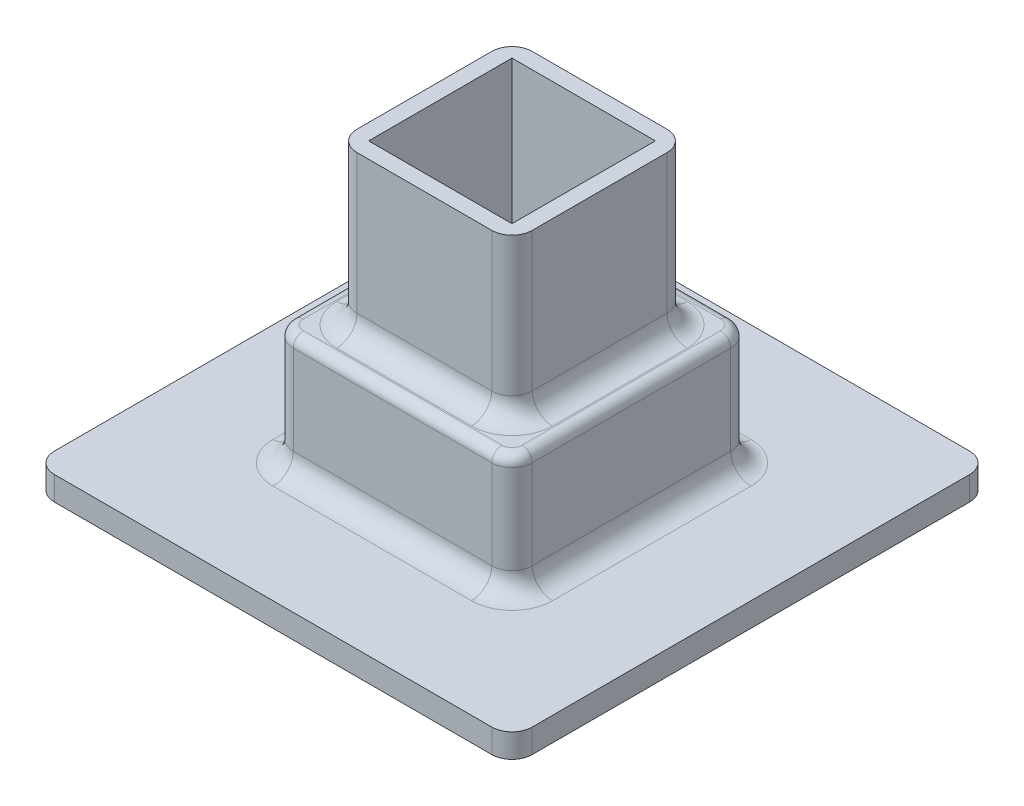
SolidWorks part; units mm, degrees
material "ABS"
ref_plane "Front Plane" through (0, 0, 0) normal (0, 0, 1) x (1, 0, 0)
ref_plane "Top Plane" through (0, 0, 0) normal (0, 1, 0) x (1, 0, 0)
ref_plane "Right Plane" through (0, 0, 0) normal (1, 0, 0) x (0, 0, -1)
sketch "Sketch1" plane through (0, 0, 0) normal (0, 1, 0) x (1, 0, 0)
  line L1 (-30, 30) -> (30, 30)
  line L2 (-30, 30) -> (-30, -30)
  line L3 (-30, -30) -> (30, -30)
  line L4 (30, 30) -> (30, -30)
  point P4 (0, 30)
  point P6 (30, 0)
  dimension "D1" = 60
extrude "Boss-Extrude1" add sketch "Sketch1" along normal blind 3
sketch "Sketch2" plane through (0, 3, 0) normal (0, 1, 0) x (1, 0, 0)
  line L1 (-15, 15) -> (15, 15)
  line L2 (-15, 15) -> (-15, -15)
  line L3 (-15, -15) -> (15, -15)
  line L4 (15, 15) -> (15, -15)
  point P4 (0, 15)
  point P6 (15, 0)
  dimension "D1" = 30
extrude "Boss-Extrude2" add sketch "Sketch2" along normal blind 15
sketch "Sketch3" plane through (0, 18, 0) normal (0, 1, 0) x (1, 0, 0)
  line L1 (-11, -11) -> (11, -11)
  line L2 (-11, -11) -> (-11, 11)
  line L3 (-11, 11) -> (11, 11)
  line L4 (11, -11) -> (11, 11)
  point P4 (-11, 0)
  point P7 (0, 11)
  dimension "22mm" = 22
extrude "Boss-Extrude3" add sketch "Sketch3" along normal blind 20
shell "Shell1" thickness 3 removed face at (0, 0, 0)
sketch "Sketch4" plane through (0, 35, 0) normal (0, -1, 0) x (1, 0, 0)
  line L4 (-8, 8) -> (-8, -8)
  line L5 (-8, -8) -> (8, -8)
  line L6 (8, -8) -> (8, 8)
  line L7 (8, 8) -> (-8, 8)
  line L8 (-8, 8) -> (-8, -8)
  line L9 (-8, -8) -> (8, -8)
  line L10 (8, -8) -> (8, 8)
  line L11 (8, 8) -> (-8, 8)
  dimension "D1" = 0
extrude "Cut-Extrude1" cut sketch "Sketch4" against normal through all
sketch "Sketch5" plane through (0, 38, 0) normal (0, 1, 0) x (1, 0, 0)
  line L1 (-9, -9) -> (9, -9)
  line L2 (-9, -9) -> (-9, 9)
  line L3 (-9, 9) -> (9, 9)
  line L4 (9, -9) -> (9, 9)
  line L20 (8, 8) -> (8, -8) construction
  line L21 (8, -8) -> (-8, -8) construction
  line L22 (-8, -8) -> (-8, 8) construction
  line L23 (-8, 8) -> (8, 8) construction
  line L24 (8, 8) -> (8, -8)
  line L25 (8, -8) -> (-8, -8)
  line L26 (-8, -8) -> (-8, 8)
  line L27 (-8, 8) -> (8, 8)
  point P12 (-9, 0)
  point P14 (0, -8)
  dimension "D1" = 1
  dimension "D2" = 1
  dimension "D3" = 1
extrude "Cut-Extrude2" cut sketch "Sketch5" against normal blind 21
fillet "Fillet2" radius 2.54 12 edges at (-12, 0, 0) (0, 0, -12) (0, 0, 12) (12, 7.5, -12) (12, 15, 0) (12, 7.5, 12) (12, 0, 0) (-12, 7.5, 12) (0, 15, 12) (-12, 15, 0) (0, 15, -12) (-12, 7.5, -12)
fillet "Fillet3" radius 2.54 20 edges at (-15, 3, 0) (0, 18, 11) (0, 3, 15) (0, 3, -15) (11, 18, 0) (-11, 18, 0) (30, 1.5, -30) (30, 1.5, 30) (-30, 1.5, -30) (-30, 1.5, 30) (15, 3, 0) (15, 10.5, -15) (15, 10.5, 15) (-15, 10.5, 15) (-15, 10.5, -15) (0, 18, -11) (11, 28, -11) (-11, 28, -11) (11, 28, 11) (-11, 28, 11)
fillet "Fillet4" radius 1.27 8 edges at (-14.2561, 18, -14.2561) (0, 18, -15) (14.2561, 18, -14.2561) (15, 18, 0) (14.2561, 18, 14.2561) (0, 18, 15) (-14.2561, 18, 14.2561) (-15, 18, 0)
